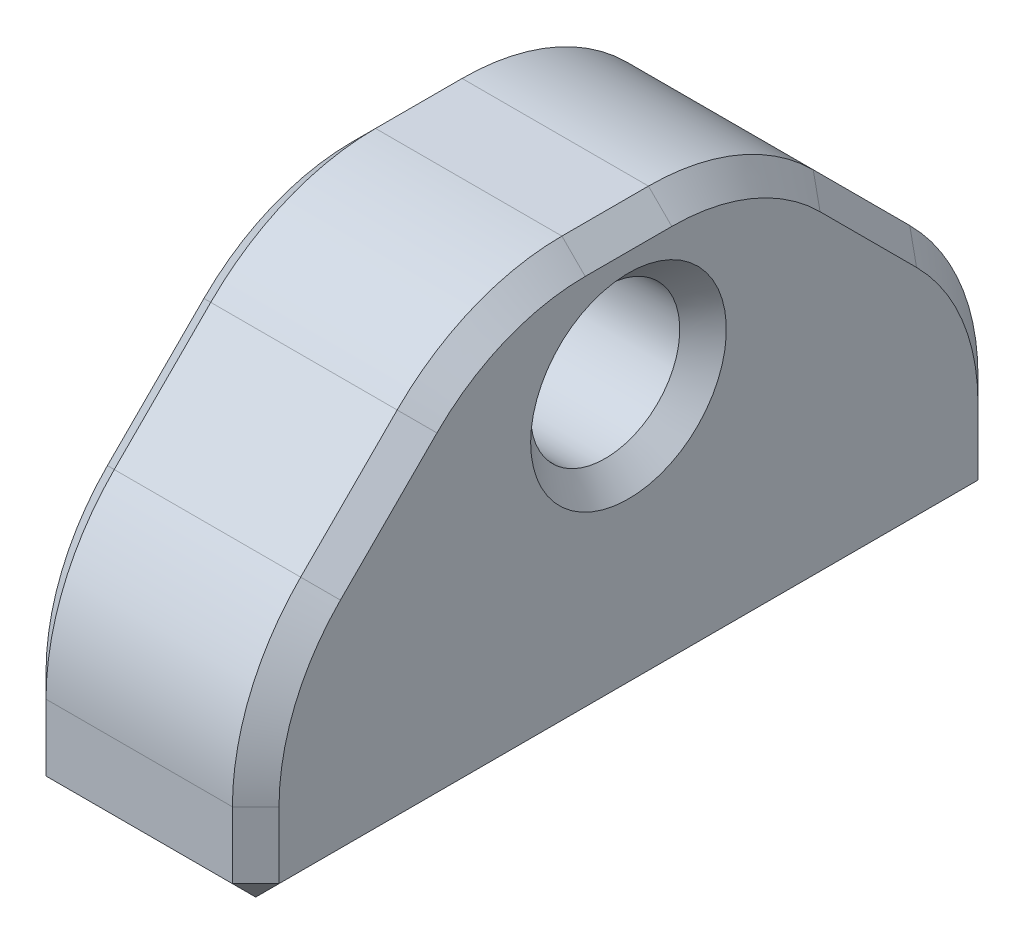
SolidWorks part; units mm, degrees
ref_plane "Front Plane" through (0, 0, 0) normal (0, 0, 1) x (1, 0, 0)
ref_plane "Top Plane" through (0, 0, 0) normal (0, 1, 0) x (1, 0, 0)
ref_plane "Right Plane" through (0, 0, 0) normal (1, 0, 0) x (0, 0, -1)
sketch "Sketch1" plane through (0, 0, 0) normal (0, 1, 0) x (1, 0, 0)
  line L0 (0, -6.35) -> (0, 6.35) construction
  line L1 (-3.175, -10.16) -> (3.175, -10.16)
  line L2 (-3.175, -10.16) -> (-3.175, 10.16)
  line L3 (-3.175, 10.16) -> (3.175, 10.16)
  line L4 (3.175, -10.16) -> (3.175, 10.16)
  line L5 (-3.175, -10.16) -> (3.175, 10.16) construction
  line L6 (-3.175, 10.16) -> (3.175, -10.16) construction
  circle A0 centre (0, 6.35) radius 2.032
  circle A1 centre (0, -6.35) radius 2.032
  point P0 (0, 0)
  point P10 (0, 0)
  dimension "D3" = 4.064
  dimension "D1" = 6.35
  dimension "D2" = 20.32
  dimension "D4" = 12.7
extrude "Boss-Extrude1" add sketch "Sketch1" along normal blind 11.43 contours L1 L4 L3 L2 A1 A0 | A1 | A0 region at (0, 0, 0) region at (0, 0, -6.35) region at (0, 0, 6.35)
extrude "Cut-Extrude1" cut sketch "Sketch1<3>" along normal blind 6.35 contours A1 | A0
sketch "Sketch1<3>" plane through (0, 0, 0) normal (0, 1, 0) x (1, 0, 0) same geometry as "Sketch1"
sketch "Sketch2" plane through (3.175, 0, 0) normal (1, 0, 0) x (0, 0, -1)
  line L0 (-10.16, 11.43) -> (-10.16, 0) construction
  circle A0 centre (0, 7.62) radius 2.032
  point P5 (-7.0372, 3.7229)
  dimension "D1" = 4.064
  dimension "D2" = 7.62
  dimension "D3" = 10.16
extrude "Cut-Extrude2" cut sketch "Sketch2" against normal through all contours A0
chamfer "Chamfer1" distance 6.35 angle 45 2 edges at (0, 11.43, -10.16) (0, 11.43, 10.16)
fillet "Fillet1" radius 6.35 2 edges at (0, 11.43, -3.81) (0, 11.43, 3.81)
fillet "Fillet2" radius 6.35 2 edges at (0, 5.08, -10.16) (0, 5.08, 10.16)
chamfer "Chamfer2" distance 0.635 angle 45 22 edges at (3.175, 0, 0) (0, 0, -10.16) (-3.175, 0, 0) (0, 0, 10.16) (-3.175, 1.2249, -10.16) (-3.175, 4.8798, -9.6766) (-3.175, 1.2249, 10.16) (-3.175, 8.255, -6.985) (-3.175, 4.8798, 9.6766) (-3.175, 10.9466, -3.6098) (-3.175, 8.255, 6.985) (-3.175, 11.43, 0) (-3.175, 10.9466, 3.6098) (3.175, 1.2249, -10.16) (3.175, 4.8798, -9.6766) (3.175, 8.255, -6.985) (3.175, 1.2249, 10.16) (3.175, 10.9466, -3.6098) (3.175, 4.8798, 9.6766) (3.175, 11.43, 0) (3.175, 8.255, 6.985) (3.175, 10.9466, 3.6098)
chamfer "Chamfer3" distance 0.635 angle 45 4 edges at (3.175, 7.62, -2.032) (-3.175, 7.62, -2.032) (0, 0, -4.318) (0, 0, 8.382)
